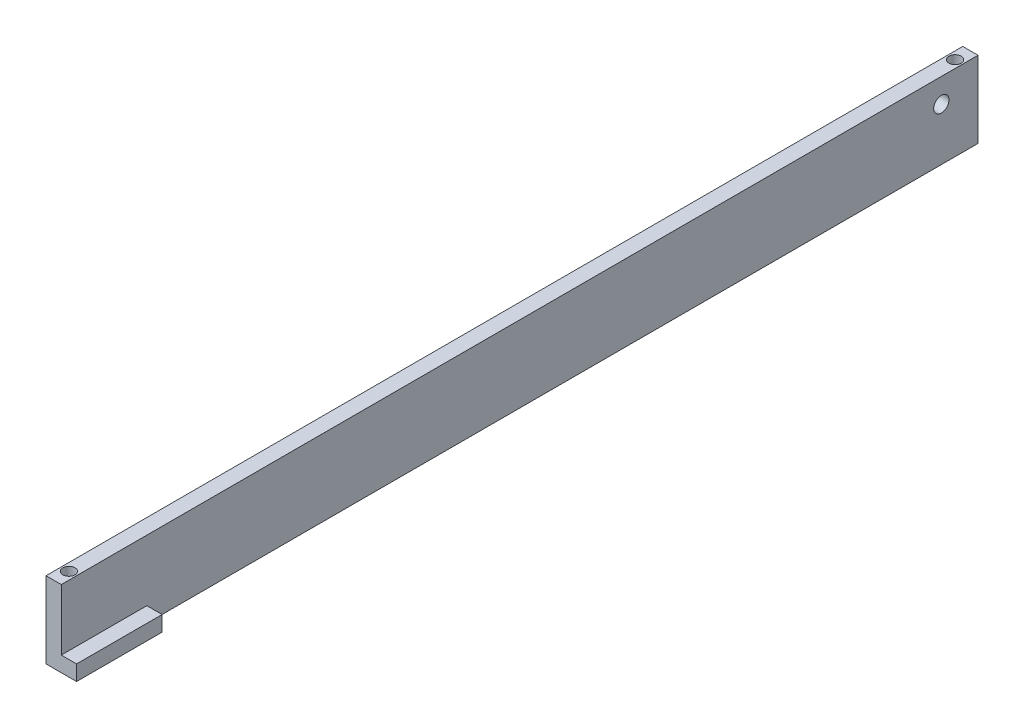
SolidWorks part; units mm, degrees
other "Markup1"
sketch "Sketch6" plane through (0, 0, 0) normal (0.7258, -0.6292, 0.2781) x (-0.261, -0.6259, -0.735)
ref_plane "Front Plane" through (0, 0, 0) normal (0, 0, 1) x (1, 0, 0)
ref_plane "Top Plane" through (0, 0, 0) normal (0, 1, 0) x (1, 0, 0)
ref_plane "Right Plane" through (0, 0, 0) normal (1, 0, 0) x (0, 0, -1)
sketch "Sketch1" plane through (0, 0, 0) normal (0, 0, 1) x (1, 0, 0)
  line L0 (0, 0) -> (-12.7, 0)
  line L1 (-12.7, 0) -> (-12.7, 31.75)
  line L2 (-12.7, 31.75) -> (-6.35, 31.75)
  line L3 (-6.35, 31.75) -> (-6.35, 6.35)
  line L4 (-6.35, 6.35) -> (0, 6.35)
  line L5 (0, 6.35) -> (0, 0)
  dimension "D1" = 6.35
  dimension "D2" = 6.35
  dimension "D3" = 6.35
  dimension "D4" = 25.4
extrude "Boss-Extrude1" add sketch "Sketch1" against normal blind 381
sketch "Sketch2" plane through (-12.7, 0, 0) normal (-1, 0, 0) x (0, 0, 1)
  line L1 (-381, 31.75) -> (0, 31.75) construction
  line L2 (0, 31.75) -> (0, 0) construction
  circle A0 centre (-365.76, 21.75) radius 3.175
  point P6 (0, 0)
  dimension "D1" = 6.35
  dimension "D2" = 10
  dimension "D3" = 365.76
extrude "Cut-Extrude1" cut sketch "Sketch2" against normal up to next
sketch "Sketch3" plane through (0, 31.75, 0) normal (0, 1, 0) x (1, 0, 0)
  line L0 (-9.525, 381) -> (-9.525, 0) construction
  line L1 (-6.35, 381) -> (-12.7, 381) construction
  line L2 (-6.35, 0) -> (-12.7, 0) construction
  circle A0 centre (-9.525, 6.35) radius 2.54
  circle A1 centre (-9.525, 374.65) radius 2.54
  dimension "D1" = 5.08
  dimension "D3" = 6.35
  dimension "D2" = 6.35
extrude "Cut-Extrude2" cut sketch "Sketch3" against normal blind 7.62
sketch "Sketch4" plane through (0, 0, 0) normal (0, -1, 0) x (1, 0, 0)
  line L0 (-9.525, 0) -> (-9.525, -381) construction
  line L1 (-12.7, 0) -> (0, 0) construction
  line L2 (-12.7, -381) -> (0, -381) construction
  line L3 (0, -381) -> (0, 0) construction
  circle A0 centre (-9.525, -374.65) radius 2.54
  circle A1 centre (-9.525, -6.35) radius 2.54
  dimension "D2" = 5.08
  dimension "D1" = 9.525
  dimension "D3" = 6.35
  dimension "D4" = 6.35
extrude "Cut-Extrude3" cut sketch "Sketch4" against normal blind 7.62
sketch "Sketch5" plane through (0, 0, -381) normal (0, 0, -1) x (-1, 0, 0)
  line L1 (6.35, 6.35) -> (0, 6.35)
  line L2 (6.35, 6.35) -> (6.35, 0)
  line L3 (6.35, 0) -> (0, 0)
  line L4 (0, 6.35) -> (0, 0)
extrude "Cut-Extrude4" cut sketch "Sketch5" against normal blind 345.44
